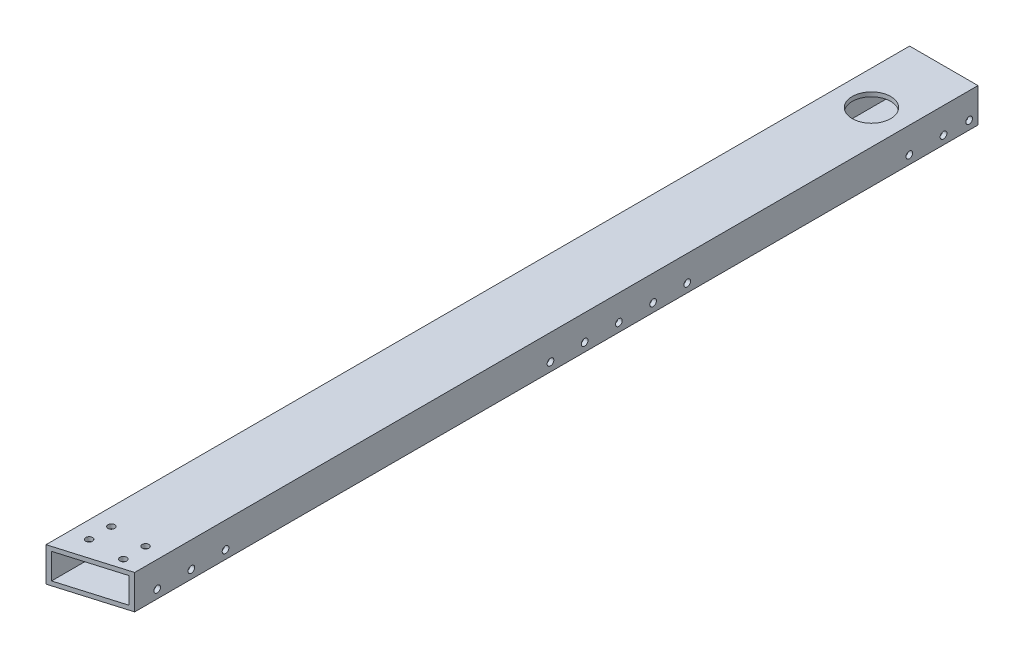
SolidWorks part; units mm, degrees
ref_plane "Front Plane" through (0, 0, 0) normal (0, 0, 1) x (1, 0, 0)
ref_plane "Top Plane" through (0, 0, 0) normal (0, 1, 0) x (1, 0, 0)
ref_plane "Right Plane" through (0, 0, 0) normal (1, 0, 0) x (0, 0, -1)
sketch "Sketch1" plane through (0, 0, 0) normal (0, 0, 1) x (1, 0, 0)
  line L0 (-22.225, 9.525) -> (22.225, 9.525)
  line L2 (-25.4, 12.7) -> (25.4, 12.7)
  line L3 (-25.4, 12.7) -> (-25.4, -12.7)
  line L4 (-25.4, -12.7) -> (25.4, -12.7)
  line L5 (25.4, 12.7) -> (25.4, -12.7)
  line L10 (22.225, 9.525) -> (22.225, -9.525)
  line L11 (-22.225, -9.525) -> (22.225, -9.525)
  line L12 (-22.225, 9.525) -> (-22.225, -9.525)
  point P12 (0, 12.7)
  point P14 (25.4, 0)
  dimension "Wall Thickness" = 3.175
  dimension "Outside Width" = 50.8
  dimension "Outside Height" = 25.4
  dimension "Inside Height" = 19.05
  dimension "Inside Width" = 44.45
sketch "Sketch2" plane through (0, 0, 0) normal (1, 0, 0) x (0, 0, -1)
  line L0 (320.675, 0) -> (-320.675, 0)
  point P4 (0, 0)
  point P7 (-320.675, 0)
  point P10 (320.675, 0)
  dimension "Length" = 641.35
sketch "Sketch3" plane through (0, 0, 0) normal (0, 0, 1) x (1, 0, 0)
  line L21 (25.4, 12.7) -> (-25.4, 12.7)
  line L22 (25.4, -12.7) -> (25.4, 12.7)
  line L23 (-25.4, -12.7) -> (25.4, -12.7)
  line L24 (-25.4, 12.7) -> (-25.4, -12.7)
  line L25 (25.4, 12.7) -> (-25.4, 12.7)
  line L26 (25.4, -12.7) -> (25.4, 12.7)
  line L27 (-25.4, -12.7) -> (25.4, -12.7)
  line L28 (-25.4, 12.7) -> (-25.4, -12.7)
  line L29 (22.225, 9.525) -> (-22.225, 9.525)
  line L30 (22.225, -9.525) -> (22.225, 9.525)
  line L31 (-22.225, -9.525) -> (22.225, -9.525)
  line L32 (-22.225, 9.525) -> (-22.225, -9.525)
  line L33 (22.225, 9.525) -> (-22.225, 9.525)
  line L34 (22.225, -9.525) -> (22.225, 9.525)
  line L35 (-22.225, -9.525) -> (22.225, -9.525)
  line L36 (-22.225, 9.525) -> (-22.225, -9.525)
  dimension "D1" = 0
  dimension "D2" = 0
extrude "Boss-Extrude1" add sketch "Sketch3" along normal up to vertex (320.675 mm away) and the other way up to vertex (320.675 mm away) up to point (0, 0, 320.675) other way up to point (0, 0, -320.675)
sketch "Drawing Reference" plane through (0, 0, 0) normal (1, 0, 0) x (0, 0, -1)
  line L0 (-320.675, 0) -> (320.675, 0) construction
  line L1 (0, -12.7) -> (0, 12.7) construction
  line L2 (-320.675, -12.7) -> (320.675, -12.7) construction
  line L5 (-320.675, 12.7) -> (320.675, 12.7) construction
  point P7 (-284.099, 0)
  point P8 (284.099, 0)
  dimension "D1" = 36.576
sketch "Sketch4" plane through (0, 12.7, 0) normal (0, 1, 0) x (1, 0, 0)
  line L0 (-25.4, -320.675) -> (25.4, -305.6274)
  line L1 (25.4, -320.675) -> (25.4, 320.675) construction
  line L2 (25.4, -320.675) -> (-25.4, -320.675)
  dimension "D1" = 16.5
extrude "Cut-Extrude1" cut sketch "Sketch4" against normal through all and the other way through all flip side to cut
sketch "Sketch8" plane through (0, 12.7, 0) normal (0, 1, 0) x (1, 0, 0)
  line L0 (0, 320.675) -> (0, 266.954) construction
  line L1 (25.4, 320.675) -> (-25.4, 320.675) construction
  circle A0 centre (0, 266.954) radius 14.2875
  dimension "D1" = 53.721
extrude "Cut-Extrude2" cut sketch "Sketch8" against normal through all
sketch "Sketch9" plane through (0, 12.7, 0) normal (0, 1, 0) x (1, 0, 0)
  line L0 (-12.7762, -284.753) -> (12.6238, -284.753) construction
  line L1 (12.6238, -284.753) -> (12.6238, -301.263) construction
  line L2 (12.6238, -301.263) -> (-12.7762, -301.263) construction
  line L3 (-12.7762, -301.263) -> (-12.7762, -284.753) construction
hole_wizard "#10 Clearance Hole1" positions "Sketch10" profile "Sketch11" hole size "#10" standard "ANSI Inch"
sketch "Sketch10" plane through (0, 12.7, 0) normal (0, 1, 0) x (1, 0, 0)
  point P0 (-12.7762, -284.753)
  point P3 (12.6238, -284.753)
  point P6 (12.6238, -301.263)
  point P9 (-12.7762, -301.263)
sketch "Sketch11" plane through (-12.7762, 12.7, 284.753) normal (1, 0, 0) x (0, 0, 1)
  line L0 (0, 0) -> (0, 6.5757)
  line L1 (0, 6.5757) -> (2.4892, 5.08)
  line L2 (2.4892, 5.08) -> (2.4892, 0)
  line L5 (2.4892, 0) -> (0, 0)
  line L10 (0, 6.5757) -> (-2.4892, 5.08) construction
  line L11 (0, -6.35) -> (0, 107.95) construction
  dimension "Hole Dia." = 4.9784
  dimension "Hole Depth" = 5.08
  dimension "Drill Angle" = 118
hole_wizard "#10 Clearance Hole2" positions "Sketch12" profile "Sketch13" hole size "#10" standard "ANSI Inch" end condition through all
sketch "Sketch12" plane through (25.4, 0, 0) normal (1, 0, 0) x (0, 0, -1)
  point P9 (3.175, -6.35)
  point P12 (28.575, -6.35)
  point P15 (53.975, -6.35)
  point P18 (79.375, -6.35)
  point P21 (104.775, -6.35)
  point P24 (-288.925, -6.35)
  point P27 (-263.525, -6.35)
  point P30 (-238.1261, -6.3882)
sketch "Sketch13" plane through (25.4, -6.35, -3.175) normal (0, 1, 0) x (0, 0, -1)
  line L0 (0, 0) -> (0, 50.8)
  line L1 (0, 50.8) -> (2.4892, 50.8)
  line L2 (2.4892, 50.8) -> (2.4892, 0)
  line L5 (2.4892, 0) -> (0, 0)
  line L11 (0, -6.35) -> (0, 107.95) construction
  dimension "Thru Hole Dia." = 4.9784
  dimension "Thru Hole Depth" = 50.8
hole_wizard "#10 Clearance Hole3" positions "Sketch14" profile "Sketch15" hole size "#10" standard "ANSI Inch"
sketch "Sketch14" plane through (25.4, 0, 0) normal (1, 0, 0) x (0, 0, -1)
  point P0 (269.6733, -6.3882)
  point P3 (295.0733, -6.3882)
  point P6 (314.1233, -6.3882)
sketch "Sketch15" plane through (25.4, -6.3882, -269.6733) normal (0, 1, 0) x (0, 0, -1)
  line L0 (0, 0) -> (0, 4.7977)
  line L1 (0, 4.7977) -> (2.4892, 3.302)
  line L2 (2.4892, 3.302) -> (2.4892, 0)
  line L5 (2.4892, 0) -> (0, 0)
  line L10 (0, 4.7977) -> (-2.4892, 3.302) construction
  line L11 (0, -6.35) -> (0, 107.95) construction
  dimension "Hole Dia." = 4.9784
  dimension "Hole Depth" = 3.302
  dimension "Drill Angle" = 118
equation "\"D1@Drawing Reference\"=\"Outside Width@Sketch1\" * 0.72"
